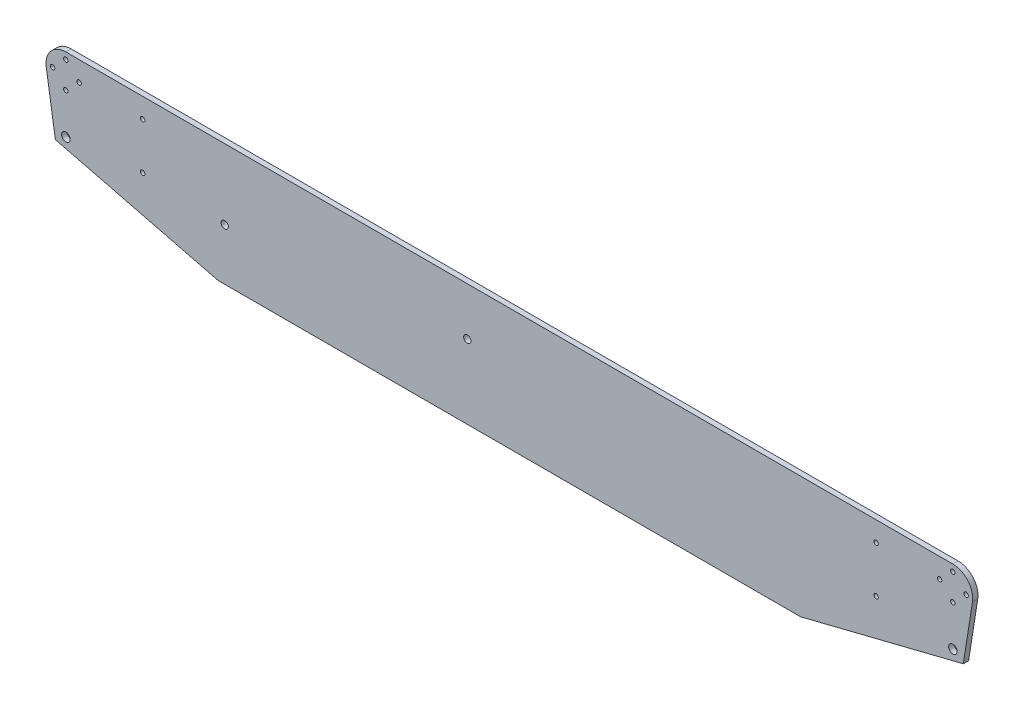
SolidWorks part; units mm, degrees
material "Сплав 2024"
ref_plane "Спереди" through (0, 0, 0) normal (0, 0, 1) x (1, 0, 0)
ref_plane "Сверху" through (0, 0, 0) normal (0, 1, 0) x (1, 0, 0)
ref_plane "Справа" through (0, 0, 0) normal (1, 0, 0) x (0, 0, -1)
sketch "Эскиз1" plane through (0, 0, 0) normal (0, 0, 1) x (1, 0, 0)
  line L0 (-349.8183, 28.6724) -> (-342.9109, -15.3036)
  line L1 (-350, 46) -> (350, 46) construction
  line L2 (-350, 46) -> (-350, -46) construction
  line L3 (-350, -46) -> (350, -46) construction
  line L4 (350, 46) -> (350, -46) construction
  line L5 (-350, 46) -> (350, -46) construction
  line L6 (-350, -46) -> (350, 46) construction
  line L7 (-342.9109, -15.3036) -> (-220, -46)
  line L9 (0, 62.4154) -> (0, -74.3401) construction
  line L10 (-220, -46) -> (220, -46)
  line L12 (-335, 46) -> (335, 46)
  line L15 (342.9109, -15.3036) -> (220, -46)
  line L16 (349.8183, 28.6724) -> (342.9109, -15.3036)
  arc A0 (-335, 46) -> (-349.8183, 28.6724) centre (-335, 31) ccw
  arc A1 (335, 46) -> (349.8183, 28.6724) centre (335, 31) cw
  circle A2 centre (-335, -9.6353) radius 3.25
  circle A3 centre (335, -9.6353) radius 3.25
  point P0 (0, 0)
  point P20 (0, 46)
  point P21 (0, -46)
  dimension "D3" = 30
  dimension "D4" = 6.5
  dimension "D1" = 700
  dimension "D2" = 92
  dimension "D5" = 440
extrude "Бобышка-Вытянуть1" add sketch "Эскиз1" along normal blind 4
sketch "Эскиз2" plane through (0, 0, 4) normal (0, 0, 1) x (1, 0, 0)
  line L0 (0, 49.4785) -> (0, -75.5602) construction
  line L1 (-350, 31) -> (-320, 31) construction
  line L2 (-335, 46) -> (-335, 16) construction
  line L3 (335, 46) -> (335, 16) construction
  line L4 (350, 31) -> (320, 31) construction
  circle A0 centre (-335, 31) radius 15 construction
  arc A1 (-335, 46) -> (-349.8183, 28.6724) centre (-335, 31) ccw construction
  circle A2 centre (-335, 31) radius 10 construction
  circle A4 centre (335, 31) radius 10 construction
  circle A5 centre (335, 31) radius 15 construction
  dimension "D2" = 20
hole_wizard "Отверстие с зазором M32" positions "Эскиз4" profile "Эскиз3" hole size "M3" standard "Ansi Metric" end condition through all
sketch "Эскиз4" plane through (0, 0, 4) normal (0, 0, 1) x (1, 0, 0)
  line L0 (-335, 46) -> (-335, 16) construction
  line L1 (-350, 31) -> (-320, 31) construction
  line L2 (350, 31) -> (320, 31) construction
  line L3 (335, 46) -> (335, 16) construction
  circle A0 centre (-335, 31) radius 10 construction
  circle A1 centre (335, 31) radius 10 construction
  point P0 (-335, 41)
  point P6 (-345, 31)
  point P10 (-335, 21)
  point P12 (-325, 31)
  point P34 (325, 31)
  point P40 (335, 41)
  point P44 (345, 31)
  point P46 (335, 21)
sketch "Эскиз3" plane through (-335, 41, 4) normal (1, 0, 0) x (0, -1, 0)
  line L0 (0, 0) -> (0, 4)
  line L1 (0, 4) -> (1.7, 4)
  line L2 (1.7, 4) -> (1.7, 0)
  line L5 (1.7, 0) -> (0, 0)
  line L11 (0, -6.35) -> (0, 107.95) construction
  dimension "Диаметр сквозного отверстия" = 3.4
  dimension "Глубина сквозного отверстия" = 4
sketch "Эскиз7" plane through (0, 0, 0) normal (0, 0, -1) x (-1, 0, 0)
  line L1 (220, -46) -> (-220, -46) construction
  arc A1 (349.8183, 28.6724) -> (335, 46) centre (335, 31) ccw construction
  point P4 (215, -7)
  dimension "D1" = 120
  dimension "D2" = 39
hole_wizard "Отверстие с зазором M52" positions "Эскиз9" profile "Эскиз8" hole size "M5" standard "Ansi Metric" end condition through all
sketch "Эскиз9" plane through (0, 0, 0) normal (0, 0, -1) x (-1, 0, 0)
  point P3 (215, -7)
sketch "Эскиз8" plane through (-215, -7, 0) normal (1, 0, 0) x (0, 1, 0)
  line L0 (0, 0) -> (0, 4)
  line L1 (0, 4) -> (2.75, 4)
  line L2 (2.75, 4) -> (2.75, 0)
  line L5 (2.75, 0) -> (0, 0)
  line L11 (0, -6.35) -> (0, 107.95) construction
  dimension "Диаметр сквозного отверстия" = 5.5
  dimension "Глубина сквозного отверстия" = 4
sketch "Эскиз10" plane through (0, 0, 4) normal (0, 0, 1) x (1, 0, 0)
  line L0 (-299.3246, 36) -> (-255.3246, 36)
  line L1 (335, 46) -> (-335, 46) construction
  line L2 (-299.3246, 36) -> (-299.3246, -15.8819)
  line L3 (-299.3246, -15.8819) -> (-242.7378, -30.0142)
  line L4 (0, 46) -> (0, -46) construction
  line L5 (-342.9109, -15.3036) -> (-220, -46) construction
  line L6 (-225.2731, 36) -> (-56.1536, 36)
  line L7 (-218.7702, -36) -> (-53.9475, -36)
  line L8 (-220, -46) -> (220, -46) construction
  line L9 (-255.3246, 36) -> (-242.1182, -22.5883)
  line L11 (-300.3246, -20.6159) -> (-300.3246, 44.3841) construction
  line L12 (271.818, 36) -> (271.818, -17.9187)
  line L13 (271.818, -17.9187) -> (224.0901, -33.1261)
  line L14 (271.818, 36) -> (224.0901, 36)
  line L15 (224.0901, 36) -> (224.0901, -33.1261)
  line L17 (212.0901, 36) -> (121.9708, 36)
  line L19 (-272.0608, -22.6909) -> (-172.0824, -47.66) construction
  line L20 (0.7585, 21.0494) -> (0.7585, -36)
  line L21 (0.7585, -36) -> (18.1269, -36)
  line L22 (212.0901, -21.0494) -> (212.0901, 36)
  line L23 (65.0489, 36) -> (65.0489, -21.0494)
  line L24 (75.0489, 21.0494) -> (75.0489, -36)
  line L25 (47.6805, 36) -> (0.7585, 21.0494)
  line L26 (212.0901, -21.0494) -> (165.1682, -36)
  line L27 (-140.8515, 55.5349) -> (-140.8515, -67.5658) construction
  line L28 (75.0489, -36) -> (165.1682, -36)
  line L29 (121.9708, 36) -> (75.0489, 21.0494)
  line L30 (65.0489, -21.0494) -> (18.1269, -36)
  line L31 (-218.7702, -36) -> (-216.2831, -6.1906)
  line L32 (-225.2731, 36) -> (-216.5143, -2.8572)
  line L33 (-164.0688, -36) -> (-228.2742, -36) construction
  line L34 (65.0489, 36) -> (47.6805, 36)
  line L35 (-242.1182, -22.5883) -> (-242.7378, -30.0142)
  line L36 (272.818, 44.3841) -> (272.818, -20.6159) construction
  line L37 (223.0901, 43) -> (223.0901, -42) construction
  line L38 (213.0901, 43) -> (213.0901, -42) construction
  arc A0 (-53.9475, -36) -> (-56.1536, 36) centre (-227.2451, -5.276) ccw
  arc A1 (-216.5143, -2.8572) -> (-216.2831, -6.1906) centre (-227.2451, -5.276) cw
  dimension "D4" = 1
  dimension "D5" = 1
  dimension "D2" = 1
  dimension "D10" = 11
  dimension "D12" = 176
  dimension "D1" = 10
  dimension "D3" = 10
  dimension "D6" = 10
  dimension "D7" = 10
  dimension "D8" = 1
  dimension "D9" = 44
  dimension "D11" = 57.0494
extrude "Вырез-Вытянуть3" [suppressed] cut sketch "Эскиз10" against normal through all
fillet "Скругление2" [suppressed] radius 10
fillet "Скругление3" [suppressed] radius 10
sketch "Эскиз14" plane through (0, 0, 4) normal (0, 0, 1) x (1, 0, 0)
  line L0 (0, 59.2479) -> (0, -65.4566) construction
fillet "Скругление4" [suppressed] radius 8
sketch "Эскиз15" plane through (0, 0, 0) normal (0, 0, 1) x (1, 0, 0)
  line L0 (-350, 110.1025) -> (-350, -46) construction
  line L1 (-350, -46) -> (-196.6137, -46) construction
  line L2 (-220, -46) -> (220, -46) construction
  line L3 (350, 94.0601) -> (350, -69.6023) construction
  arc A0 (-335, 46) -> (-349.8183, 28.6724) centre (-335, 31) ccw construction
  arc A1 (349.8183, 28.6724) -> (335, 46) centre (335, 31) ccw construction
ref_axis "Ось1" through (0, 115.2529, 7.011) along (0, -0.9991, -0.0434)
sketch "Эскиз17" plane through (0, 0, 0) normal (0, 0, -1) x (-1, 0, 0)
  line L0 (-277, 66.2572) -> (-277, -56.845) construction
  line L1 (-335, 46) -> (335, 46) construction
  line L3 (0, 46) -> (0, 69.3185) construction
  line L4 (0, 115.2529) -> (0, -164.0423) construction
  line L5 (220, -46) -> (-220, -46) construction
  arc A0 (-335, 46) -> (-349.8183, 28.6724) centre (-335, 31) ccw construction
  arc A1 (36.6847, -52.3836) -> (42.8196, 57.8837) centre (215, -7) cw construction
  point P2 (-277, 31)
  point P3 (-277, -4)
  point P9 (277, 31)
  point P10 (277, -4)
  point P20 (31.7713, 9.83)
  dimension "D3" = 58
  dimension "D4" = 184
  dimension "D1" = 15
  dimension "D2" = 35
  dimension "D5" = 55.83
hole_wizard "Отверстие с зазором M33" positions "Эскиз19" profile "Эскиз18" hole size "M3" standard "Ansi Metric" end condition through all
sketch "Эскиз19" plane through (0, 0, 0) normal (0, 0, -1) x (-1, 0, 0)
  point P0 (-277, 31)
  point P5 (-277, -4)
  point P8 (277, -4)
  point P11 (277, 31)
sketch "Эскиз18" plane through (277, 31, 0) normal (1, 0, 0) x (0, 1, 0)
  line L0 (0, 0) -> (0, 4)
  line L1 (0, 4) -> (1.7, 4)
  line L2 (1.7, 4) -> (1.7, 0)
  line L5 (1.7, 0) -> (0, 0)
  line L11 (0, -6.35) -> (0, 107.95) construction
  dimension "Диаметр сквозного отверстия" = 3.4
  dimension "Глубина сквозного отверстия" = 4
hole_wizard "Отверстие с зазором M53" positions "Эскиз21" profile "Эскиз20" hole size "M5" standard "Ansi Metric" end condition through all
sketch "Эскиз21" plane through (0, 0, 0) normal (0, 0, -1) x (-1, 0, 0)
  point P0 (31.7713, 9.83)
sketch "Эскиз20" plane through (-31.7713, 9.83, 0) normal (1, 0, 0) x (0, 1, 0)
  line L0 (0, 0) -> (0, 4)
  line L1 (0, 4) -> (2.75, 4)
  line L2 (2.75, 4) -> (2.75, 0)
  line L5 (2.75, 0) -> (0, 0)
  line L11 (0, -6.35) -> (0, 107.95) construction
  dimension "Диаметр сквозного отверстия" = 5.5
  dimension "Глубина сквозного отверстия" = 4
